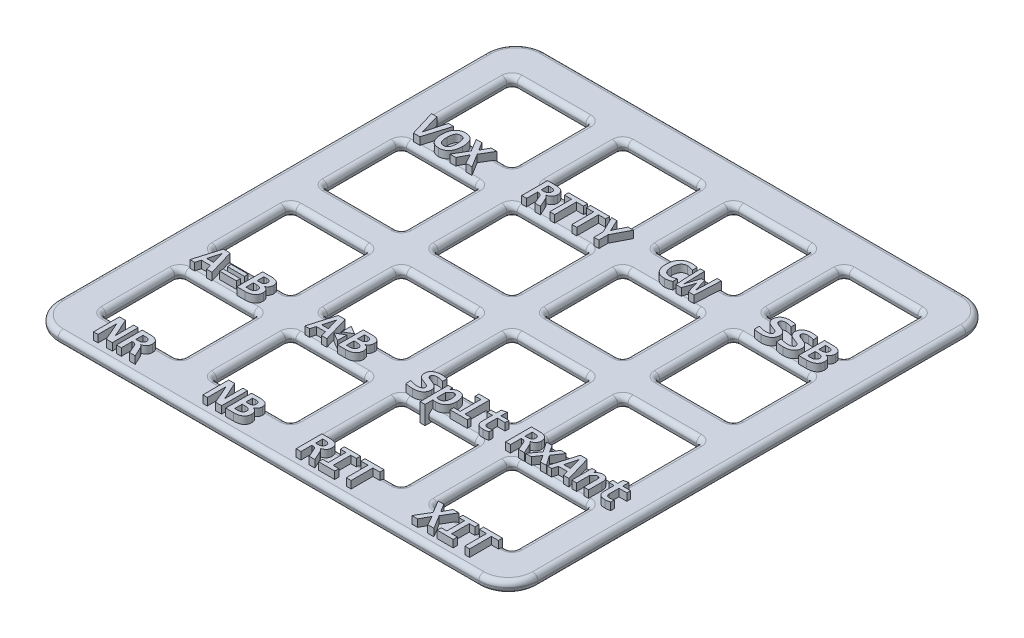
SolidWorks part; units mm, degrees
ref_plane "Front" through (0, 0, 0) normal (0, 0, 1) x (1, 0, 0)
ref_plane "Top" through (0, 0, 0) normal (0, 1, 0) x (1, 0, 0)
ref_plane "Right" through (0, 0, 0) normal (1, 0, 0) x (0, 0, -1)
sketch "Sketch1" plane through (0, 0, 0) normal (0, 1, 0) x (1, 0, 0)
  line L1 (-14.8807, -14.5355) -> (42.1193, -14.5355)
  line L2 (-18.8807, -18.5355) -> (-18.8807, -76.5355)
  line L3 (-14.8807, -80.5355) -> (42.1193, -80.5355)
  line L4 (46.1193, -18.5355) -> (46.1193, -76.5355)
  arc A0 (-14.8807, -14.5355) -> (-18.8807, -18.5355) centre (-14.8807, -18.5355) ccw
  arc A1 (46.1193, -18.5355) -> (42.1193, -14.5355) centre (42.1193, -18.5355) ccw
  arc A2 (42.1193, -80.5355) -> (46.1193, -76.5355) centre (42.1193, -76.5355) ccw
  arc A3 (-18.8807, -76.5355) -> (-14.8807, -80.5355) centre (-14.8807, -76.5355) ccw
  dimension "D1" = 65
  dimension "D2" = 66
extrude "main" add sketch "Sketch1" along normal blind 1.5
sketch "Sketch2" plane through (0, 1.5, 0) normal (0, 1, 0) x (1, 0, 0)
  line L0 (42.1193, -14.5355) -> (-14.8807, -14.5355) construction
  line L1 (-14.2307, -19.6855) -> (-3.5307, -19.6855)
  line L2 (-14.2307, -19.6855) -> (-14.2307, -30.3855)
  line L3 (-14.2307, -30.3855) -> (-3.5307, -30.3855)
  line L4 (-3.5307, -19.6855) -> (-3.5307, -30.3855)
  line L5 (-18.8807, -18.5355) -> (-18.8807, -76.5355) construction
  point P4 (-8.8807, -19.6855)
  dimension "D1" = 5.15
  dimension "D2" = 4.65
  dimension "D3" = 10.7
  dimension "D4" = 10.7
extrude "button hole 1" cut sketch "Sketch2" against normal through all
fillet "button fillet" radius 0.7 12 edges at (-8.8807, 0, 30.3855) (-8.8807, 1.5, 30.3855) (-8.8807, 0, 19.6855) (-8.8807, 1.5, 19.6855) (-3.5307, 0.75, 30.3855) (-3.5307, 0, 25.0355) (-3.5307, 0.75, 19.6855) (-3.5307, 1.5, 25.0355) (-14.2307, 0.75, 19.6855) (-14.2307, 0, 25.0355) (-14.2307, 0.75, 30.3855) (-14.2307, 1.5, 25.0355)
pattern_linear "buttons by 16" count 4 spacing 15 along (1, 0, 0) count 4 spacing 15 along (0, 0, 1) of "button fillet", "button hole 1"
fillet "outer edge fillet" radius 0.7 16 edges at (13.6193, 1.5, 14.5355) (13.6193, 0, 14.5355) (46.1193, 1.5, 47.5355) (46.1193, 0, 47.5355) (13.6193, 1.5, 80.5355) (13.6193, 0, 80.5355) (-18.8807, 1.5, 47.5355) (-18.8807, 0, 47.5355) (44.9477, 1.5, 15.7071) (44.9477, 1.5, 79.364) (-17.7092, 1.5, 79.364) (-17.7092, 1.5, 15.7071) (44.9477, 0, 15.7071) (44.9477, 0, 79.364) (-17.7092, 0, 79.364) (-17.7092, 0, 15.7071)
sketch "Lettering" plane through (0, 0, 0) normal (0, 1, 0) x (1, 0, 0)
  line L0 (45.4193, -49.1355) -> (-18.1807, -49.1355) construction
  line L1 (45.4783, -79.1355) -> (-16.5217, -79.1355) construction
  line L2 (45.4193, -76.5355) -> (45.4193, -18.5355) construction
  line L3 (-18.1807, -18.5355) -> (-18.1807, -76.5355) construction
  line L5 (45.4193, -64.1355) -> (-18.1807, -64.1355) construction
  line L6 (45.4193, -76.5355) -> (45.4193, -18.5355) construction
  line L7 (-18.1807, -18.5355) -> (-18.1807, -76.5355) construction
  line L8 (45.4193, -34.1355) -> (-18.1807, -34.1355) construction
  line L11 (-14.8807, -80.5355) -> (42.1193, -80.5355) construction
  line L16 (6.45, -61.6855) -> (5.3241, -61.0355)
  line L17 (5.3241, -61.0355) -> (5.3241, -62.3355)
  line L18 (5.3241, -62.3355) -> (6.45, -61.6855)
  line L19 (4.9405, -62.9814) -> (6.0628, -63.6376)
  line L20 (6.0628, -63.6376) -> (6.07, -62.3376)
  line L21 (6.07, -62.3376) -> (4.9405, -62.9814)
  line L26 (1.4693, -63.9855) -> (10.7693, -63.9855) construction
  circle A1 centre (5.6994, -61.6855) radius 0.3753 construction
  circle A2 centre (5.6911, -62.9855) radius 0.3753 construction
  text T0 "SSB" font "Consolas" height 3.5
  text T1 "CW" font "Consolas" height 3.5
  text T2 "RTTY" font "Consolas" height 3.5
  text T3 "VOX" font "Consolas" height 3.5
  text T4 "RxAnt" font "Consolas" height 3.5
  text T5 "Splt" font "Consolas" height 3.5
  text T6 "XIT" font "Consolas" height 3.5
  text T7 "A" font "Consolas" height 3.5
  text T9 "RIT" font "Consolas" height 3.5
  text T10 "NB" font "Consolas" height 3.5
  text T11 "NR" font "Consolas" height 3.5
  text T15 "A=B" font "Consolas" height 3.5
  text T17 "B" font "Consolas" height 3.5
  dimension "D1" = 46.4
  dimension "D2" = 16.4
  dimension "D3" = 1.4
  dimension "D4" = 31.4
  dimension "D5" = 1.3
  dimension "D6" = 1.3
  dimension "D7" = 1
extrude "lettering boss" add sketch "Lettering" along normal blind 2.5
